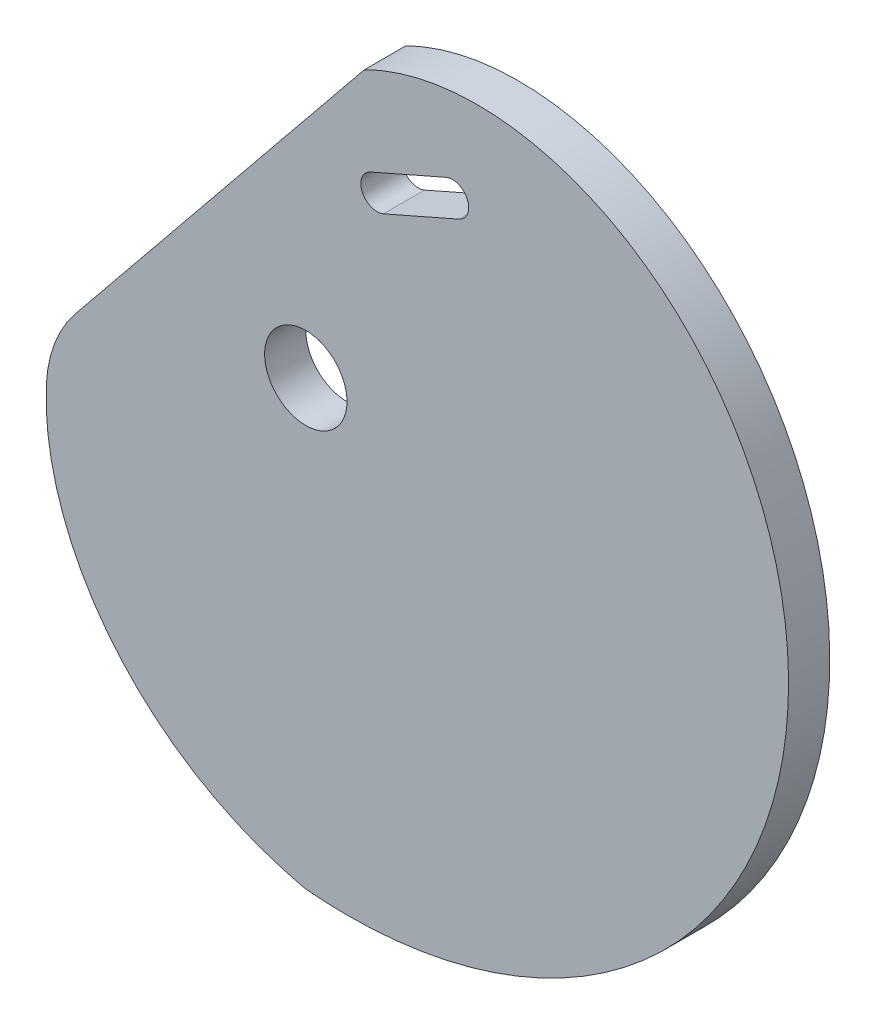
SolidWorks part; units mm, degrees
ref_plane "Front Plane" through (0, 0, 0) normal (0, 0, 1) x (1, 0, 0)
ref_plane "Top Plane" through (0, 0, 0) normal (0, 1, 0) x (1, 0, 0)
ref_plane "Right Plane" through (0, 0, 0) normal (1, 0, 0) x (0, 0, -1)
curve "Curve1"
sketch "Sketch1" plane through (0, 0, 0) normal (0, 0, 1) x (1, 0, 0)
  line L0 (10.9805, 30.1851) -> (22.6104, 35.2876) construction
  line L1 (9.976, 32.4744) -> (21.6059, 37.5769)
  line L2 (11.9849, 27.8957) -> (23.6148, 32.9983)
  line L3 (10.7688, 46.4724) -> (16.7954, 32.7363) construction
  line L4 (-15.5247, -36.542) -> (-17.0714, -47.8252) construction
  line L5 (-12.072, -37.0153) -> (-13.6188, -48.2986) construction
  line L6 (-18.9773, -36.0687) -> (-20.5241, -47.3519) construction
  line L7 (-15.1851, -34.0651) -> (-15.8642, -39.0188) construction
  circle A0 centre (0, 0) radius 6.35
  arc A1 (9.976, 32.4744) -> (11.9849, 27.8957) centre (10.9805, 30.1851) ccw
  arc A2 (23.6148, 32.9983) -> (21.6059, 37.5769) centre (22.6104, 35.2876) ccw
  arc A4 (-12.072, -37.0153) -> (-18.9773, -36.0687) centre (-15.5247, -36.542) ccw construction
  arc A5 (-20.5241, -47.3519) -> (-13.6188, -48.2986) centre (-17.0714, -47.8252) ccw construction
  spline S1 degree 3 poles (-1.1843, -67.9504) (-0.014, -68.2767) (1.195, -68.3213) (2.3889, -68.4148) (3.5889, -68.4701) (4.791, -68.5105) (5.9959, -68.5295) (7.203, -68.5287) (8.412, -68.5074) (9.6226, -68.4657) (10.8344, -68.4032) (12.047, -68.32) (13.2602, -68.2159) (14.4735, -68.0908) (15.6866, -67.9446) (16.8991, -67.777) (18.1106, -67.5882) (19.3207, -67.3779) (20.529, -67.1461) (21.7351, -66.8927) (22.9386, -66.6176) (24.1392, -66.3208) (25.3362, -66.0022) (26.5295, -65.6619) (27.7184, -65.2996) (28.9026, -64.9155) (30.0816, -64.5096) (31.2551, -64.0817) (32.4225, -63.632) (33.5833, -63.1604) (34.7372, -62.667) (35.8837, -62.1518) (37.0223, -61.6149) (38.1525, -61.0563) (39.2739, -60.4761) (40.3861, -59.8743) (41.4885, -59.2512) (42.5806, -58.6068) (43.6621, -57.9411) (44.7324, -57.2544) (45.791, -56.5468) (46.8375, -55.8184) (47.8714, -55.0695) (48.8923, -54.3001) (49.8996, -53.5105) (50.8929, -52.7009) (51.8717, -51.8715) (52.8356, -51.0225) (53.7841, -50.1542) (54.7166, -49.2668) (55.6329, -48.3607) (56.5323, -47.436) (57.4145, -46.4932) (58.279, -45.5324) (59.1254, -44.554) (59.9531, -43.5583) (60.7619, -42.5458) (61.5512, -41.5167) (62.3207, -40.4714) (63.0698, -39.4103) (63.7983, -38.3338) (64.5057, -37.2423) (65.1916, -36.1362) (65.8556, -35.016) (66.4973, -33.882) (67.1165, -32.7348) (67.7126, -31.5748) (68.2854, -30.4026) (68.8345, -29.2185) (69.3596, -28.023) (69.8603, -26.8168) (70.3364, -25.6003) (70.7876, -24.3741) (71.2134, -23.1386) (71.6138, -21.8945) (71.9884, -20.6423) (72.337, -19.3826) (72.6592, -18.116) (72.955, -16.843) (73.224, -15.5643) (73.4661, -14.2804) (73.6812, -12.992) (73.8689, -11.6997) (74.0292, -10.4042) (74.1619, -9.106) (74.2669, -7.8058) (74.3441, -6.5043) (74.3933, -5.2021) (74.4146, -3.9) (74.4078, -2.5984) (74.3729, -1.2982) (74.3098, -0.0001) (74.2186, 1.2954) (74.0993, 2.5875) (73.9518, 3.8756) (73.7762, 5.1589) (73.5725, 6.4367) (73.3409, 7.7084) (73.0814, 8.9732) (72.7942, 10.2305) (72.4792, 11.4795) (72.1368, 12.7196) (71.767, 13.95) (71.3701, 15.1701) (70.9462, 16.3792) (70.4955, 17.5765) (70.0184, 18.7613) (69.515, 19.9331) (68.9856, 21.091) (68.4305, 22.2344) (67.85, 23.3626) (67.2445, 24.475) (66.6143, 25.5709) (65.9598, 26.6495) (65.2813, 27.7103) (64.5793, 28.7526) (63.8542, 29.7758) (63.1064, 30.7792) (62.3364, 31.7621) (61.5447, 32.7241) (60.7318, 33.6643) (59.8981, 34.5824) (59.0442, 35.4776) (58.1707, 36.3494) (57.2782, 37.1972) (56.3671, 38.0204) (55.4383, 38.8186) (54.4923, 39.5913) (53.53, 40.3381) (52.552, 41.0585) (51.5591, 41.7521) (50.552, 42.4186) (49.5315, 43.0576) (48.4984, 43.6687) (47.4535, 44.2516) (46.3974, 44.8061) (45.3311, 45.3318) (44.2553, 45.8284) (43.1709, 46.2958) (42.0786, 46.7338) (40.9793, 47.1421) (39.8737, 47.5205) (38.7628, 47.869) (37.6473, 48.1874) (36.5281, 48.4755) (35.4061, 48.7334) (34.282, 48.961) (33.1567, 49.1581) (32.031, 49.3249) (30.9059, 49.4613) (29.7821, 49.5673) (28.6604, 49.6431) (27.5418, 49.6886) (26.427, 49.7041) (25.3169, 49.6895) (24.2124, 49.6451) (23.1141, 49.571) (22.0231, 49.4674) (20.94, 49.3346) (19.8657, 49.1727) (18.801, 48.982) (17.7468, 48.7628) (16.7037, 48.5154) (15.6726, 48.2401) (14.6543, 47.9373) (13.6495, 47.6073) (12.659, 47.2504) (11.6836, 46.8672) (10.7239, 46.458) (9.7807, 46.0233) (8.8547, 45.5635) (7.9467, 45.0791) (7.0573, 44.5706) (6.1871, 44.0386) (5.3369, 43.4835) (4.5074, 42.906) (3.699, 42.3065) (2.9126, 41.6858) (2.1491, 41.0448) (1.4087, 40.3857) (0.692, 39.711) (-0.0007, 39.0233) (-0.6692, 38.3252) (-1.3135, 37.6192) (-1.9336, 36.908) (-2.5298, 36.194) (-3.1024, 35.4799) (-3.6521, 34.7682) (-4.1795, 34.0612) (-4.6854, 33.3616) (-5.1709, 32.6716) (-5.637, 31.9937) (-6.085, 31.3301) (-6.5163, 30.6831) (-6.9325, 30.0548) (-7.3352, 29.4474) (-7.7263, 28.8629) (-8.1078, 28.3032) (-8.4816, 27.77) (-8.8501, 27.2652) (-9.216, 26.7897) (-9.5801, 26.3424) (-9.9432, 25.9213) (-10.3062, 25.5243) (-10.6698, 25.1494) (-11.0346, 24.7946) (-11.4009, 24.4578) (-11.7691, 24.1369) (-12.1394, 23.8299) (-12.5117, 23.5348) (-12.8861, 23.2497) (-13.2622, 22.9725) (-13.6397, 22.7014) (-14.0182, 22.4345) (-14.3971, 22.1699) (-14.7757, 21.906) (-15.1531, 21.6409) (-15.5285, 21.3732) (-15.9009, 21.1012) (-16.269, 20.8234) (-16.6317, 20.5384) (-16.9875, 20.2449) (-17.3351, 19.9417) (-17.6745, 19.6295) (-18.0059, 19.3089) (-18.3295, 18.9807) (-18.6455, 18.6455) (-18.9542, 18.3039) (-19.2559, 17.9565) (-19.5509, 17.6038) (-19.8396, 17.2464) (-20.1224, 16.8848) (-20.3997, 16.5195) (-20.672, 16.1508) (-20.9397, 15.7793) (-21.2033, 15.4052) (-21.4634, 15.0289) (-21.7205, 14.6507) (-21.9753, 14.2708) (-22.2281, 13.8895) (-22.4798, 13.507) (-22.7308, 13.1233) (-22.9819, 12.7386) (-23.2336, 12.3529) (-23.4866, 11.9663) (-23.7416, 11.5787) (-23.9993, 11.19) (-24.2602, 10.8001) (-24.5251, 10.4088) (-24.7947, 10.016) (-25.0696, 9.6214) (-25.3504, 9.2246) (-25.6379, 8.8254) (-25.9327, 8.4234) (-26.2354, 8.018) (-26.5467, 7.609) (-26.8672, 7.1956) (-27.1974, 6.7776) (-27.537, 6.3539) (-27.8856, 5.9238) (-28.2424, 5.4864) (-28.6069, 5.0408) (-28.9783, 4.5865) (-29.3562, 4.1226) (-29.7396, 3.6485) (-30.1278, 3.1637) (-30.5202, 2.6674) (-30.9158, 2.1592) (-31.314, 1.6386) (-31.7137, 1.1051) (-32.1143, 0.5583) (-32.5148, -0.0021) (-32.9143, -0.5765) (-33.3119, -1.1651) (-33.7067, -1.7682) (-34.0978, -2.3859) (-34.4843, -3.0184) (-34.8652, -3.6658) (-35.2396, -4.3281) (-35.6066, -5.0053) (-35.9651, -5.6973) (-36.3143, -6.404) (-36.6531, -7.1254) (-36.9808, -7.8611) (-37.2963, -8.611) (-37.5988, -9.3748) (-37.8873, -10.1521) (-38.1609, -10.9426) (-38.4187, -11.7459) (-38.66, -12.5613) (-38.8837, -13.3886) (-39.0892, -14.2271) (-39.2755, -15.0762) (-39.4422, -15.9354) (-39.589, -16.8043) (-39.7155, -17.6823) (-39.8215, -18.5689) (-39.9067, -19.4636) (-39.9709, -20.366) (-40.0137, -21.2755) (-40.035, -22.1916) (-40.0345, -23.1138) (-40.0119, -24.0415) (-39.9672, -24.9742) (-39.9002, -25.9114) (-39.8105, -26.8525) (-39.6982, -27.7969) (-39.563, -28.7442) (-39.4048, -29.6936) (-39.2235, -30.6448) (-39.019, -31.597) (-38.7911, -32.5497) (-38.5399, -33.5023) (-38.2653, -34.4543) (-37.9672, -35.4051) (-37.6456, -36.354) (-37.3004, -37.3005) (-36.9317, -38.2441) (-36.5395, -39.184) (-36.1238, -40.1197) (-35.6847, -41.0507) (-35.2221, -41.9763) (-34.7363, -42.896) (-34.2272, -43.8091) (-33.695, -44.715) (-33.1398, -45.6133) (-32.5617, -46.5032) (-31.9609, -47.3843) (-31.3375, -48.2559) (-30.6917, -49.1174) (-30.0238, -49.9683) (-29.3338, -50.808) (-28.6221, -51.636) (-27.8888, -52.4517) (-27.1343, -53.2545) (-26.3587, -54.0439) (-25.5624, -54.8193) (-24.7457, -55.5802) (-23.9088, -56.3261) (-23.0521, -57.0564) (-22.1759, -57.7707) (-21.2805, -58.4684) (-20.3664, -59.149) (-19.4339, -59.812) (-18.4833, -60.4569) (-17.5151, -61.0833) (-16.5298, -61.6908) (-15.5276, -62.2787) (-14.5091, -62.8467) (-13.4747, -63.3944) (-12.4248, -63.9213) (-11.36, -64.4271) (-10.2807, -64.9112) (-9.1874, -65.3733) (-8.0806, -65.8131) (-6.9608, -66.2301) (-5.8286, -66.6239) (-4.6845, -66.9947) (-3.5289, -67.3403) (-2.3631, -67.6669) (-1.1843, -67.9504) (-0.014, -68.2767) (1.195, -68.3213) knots -0.0101 -0.006743 -0.003377 0 0.00332 0.006645 0.009976 0.013312 0.016655 0.020003 0.023357 0.026716 0.030082 0.033453 0.036831 0.040214 0.043603 0.046998 0.050399 0.053806 0.057218 0.060637 0.064061 0.067491 0.070927 0.074369 0.077816 0.081269 0.084728 0.088192 0.091662 0.095138 0.098619 0.102105 0.105597 0.109094 0.112596 0.116103 0.119615 0.123133 0.126655 0.130182 0.133714 0.137251 0.140792 0.144337 0.147888 0.151442 0.155 0.158563 0.16213 0.1657 0.169275 0.172853 0.176434 0.180019 0.183607 0.187199 0.190793 0.19439 0.19799 0.201593 0.205199 0.208806 0.212416 0.216028 0.219642 0.223258 0.226875 0.230494 0.234115 0.237736 0.241359 0.244982 0.248606 0.252231 0.255856 0.259481 0.263106 0.266731 0.270356 0.273981 0.277605 0.281228 0.28485 0.28847 0.29209 0.295708 0.299324 0.302939 0.306551 0.310161 0.313769 0.317374 0.320976 0.324575 0.328171 0.331763 0.335352 0.338938 0.342519 0.346096 0.349669 0.353237 0.356801 0.360359 0.363913 0.367461 0.371004 0.374541 0.378073 0.381598 0.385117 0.38863 0.392136 0.395636 0.399128 0.402614 0.406092 0.409563 0.413026 0.416482 0.419929 0.423369 0.4268 0.430223 0.433637 0.437043 0.44044 0.443828 0.447206 0.450575 0.453935 0.457284 0.460624 0.463953 0.467272 0.47058 0.473877 0.477164 0.480439 0.483703 0.486955 0.490196 0.493426 0.496643 0.499848 0.503042 0.506223 0.509391 0.512547 0.515691 0.518822 0.52194 0.525045 0.528137 0.531216 0.534282 0.537335 0.540375 0.543401 0.546414 0.549414 0.5524 0.555374 0.558333 0.56128 0.564213 0.567133 0.57004 0.572933 0.575814 0.578681 0.581535 0.584377 0.587205 0.590021 0.592825 0.595616 0.598394 0.60116 0.603911 0.606642 0.60935 0.612032 0.614684 0.617303 0.619884 0.622424 0.62492 0.627367 0.629763 0.632104 0.634387 0.636609 0.638767 0.640858 0.64288 0.644831 0.64671 0.648517 0.65025 0.651911 0.653509 0.655048 0.656538 0.657984 0.659394 0.660772 0.662125 0.663458 0.664774 0.666078 0.667373 0.668662 0.669946 0.671227 0.672507 0.673786 0.675065 0.676344 0.677623 0.678903 0.680182 0.681461 0.68274 0.684019 0.685298 0.686575 0.687853 0.689129 0.690404 0.691679 0.692952 0.694224 0.695495 0.696765 0.698035 0.699304 0.700572 0.70184 0.703109 0.704379 0.705651 0.706925 0.708202 0.709483 0.71077 0.712063 0.713364 0.714674 0.715995 0.717328 0.718676 0.72004 0.721422 0.722825 0.72425 0.7257 0.727177 0.728683 0.730218 0.731784 0.73338 0.735008 0.736668 0.738359 0.740082 0.741837 0.743623 0.745441 0.747291 0.749171 0.751082 0.753022 0.754993 0.756992 0.759021 0.761077 0.76316 0.765271 0.767407 0.769569 0.771756 0.773967 0.776201 0.778458 0.780736 0.783036 0.785357 0.787697 0.790056 0.792433 0.794828 0.797239 0.799666 0.80211 0.804571 0.807047 0.80954 0.812049 0.814575 0.817116 0.819674 0.822248 0.824838 0.827444 0.830066 0.832704 0.835358 0.838027 0.840713 0.843414 0.846131 0.848864 0.851612 0.854376 0.857155 0.859949 0.862759 0.865584 0.868424 0.871279 0.874149 0.877033 0.879933 0.882847 0.885776 0.88872 0.891678 0.89465 0.897636 0.900637 0.903651 0.906679 0.909721 0.912777 0.915847 0.91893 0.922026 0.925135 0.928258 0.931393 0.934541 0.937702 0.940876 0.944062 0.947261 0.950471 0.953694 0.956929 0.960175 0.963433 0.966703 0.969984 0.973276 0.976579 0.979893 0.983218 0.986554 0.9899 0.993257 0.996623 1 1.00332 1.006645 1.009976 only from (0, -68.2309) to (0, -68.2309)
  point P6 (16.7954, 32.7363)
  point P18 (-16.298, -42.1836)
  dimension "D1" = 12.7
  dimension "D2" = 12.7
  dimension "D3" = 5
  dimension "D4" = 15
extrude "Boss-Extrude1" add sketch "Sketch1" along normal mid plane 6.35 contours S1 A0 A2 L2 A1 L1 region at (19.1235, -11.794, 0)
sketch "Sketch2" plane through (0, 0, 0) normal (0, 0, 1) x (1, 0, 0)
  line L0 (7.479, 46.6391) -> (-35.7001, -3.6508) construction
  line L1 (-35.7001, -3.6508) -> (-5.287, 46.6391)
  line L2 (-5.287, 46.6391) -> (7.479, 46.6391)
  line L3 (9.0178, 45.6413) -> (-41.2002, -16.1969)
  line L4 (7.479, 46.6391) -> (9.0178, 45.6413)
  line L5 (-35.7001, -3.6508) -> (-41.2002, -16.1969)
  spline S0 degree 3 poles (-1.1843, -67.9504) (-0.014, -68.2767) (1.195, -68.3213) (2.3889, -68.4148) (3.5889, -68.4701) (4.791, -68.5105) (5.9959, -68.5295) (7.203, -68.5287) (8.412, -68.5074) (9.6226, -68.4657) (10.8344, -68.4032) (12.047, -68.32) (13.2602, -68.2159) (14.4735, -68.0908) (15.6866, -67.9446) (16.8991, -67.777) (18.1106, -67.5882) (19.3207, -67.3779) (20.529, -67.1461) (21.7351, -66.8927) (22.9386, -66.6176) (24.1392, -66.3208) (25.3362, -66.0022) (26.5295, -65.6619) (27.7184, -65.2996) (28.9026, -64.9155) (30.0816, -64.5096) (31.2551, -64.0817) (32.4225, -63.632) (33.5833, -63.1604) (34.7372, -62.667) (35.8837, -62.1518) (37.0223, -61.6149) (38.1525, -61.0563) (39.2739, -60.4761) (40.3861, -59.8743) (41.4885, -59.2512) (42.5806, -58.6068) (43.6621, -57.9411) (44.7324, -57.2544) (45.791, -56.5468) (46.8375, -55.8184) (47.8714, -55.0695) (48.8923, -54.3001) (49.8996, -53.5105) (50.8929, -52.7009) (51.8717, -51.8715) (52.8356, -51.0225) (53.7841, -50.1542) (54.7166, -49.2668) (55.6329, -48.3607) (56.5323, -47.436) (57.4145, -46.4932) (58.279, -45.5324) (59.1254, -44.554) (59.9531, -43.5583) (60.7619, -42.5458) (61.5512, -41.5167) (62.3207, -40.4714) (63.0698, -39.4103) (63.7983, -38.3338) (64.5057, -37.2423) (65.1916, -36.1362) (65.8556, -35.016) (66.4973, -33.882) (67.1165, -32.7348) (67.7126, -31.5748) (68.2854, -30.4026) (68.8345, -29.2185) (69.3596, -28.023) (69.8603, -26.8168) (70.3364, -25.6003) (70.7876, -24.3741) (71.2134, -23.1386) (71.6138, -21.8945) (71.9884, -20.6423) (72.337, -19.3826) (72.6592, -18.116) (72.955, -16.843) (73.224, -15.5643) (73.4661, -14.2804) (73.6812, -12.992) (73.8689, -11.6997) (74.0292, -10.4042) (74.1619, -9.106) (74.2669, -7.8058) (74.3441, -6.5043) (74.3933, -5.2021) (74.4146, -3.9) (74.4078, -2.5984) (74.3729, -1.2982) (74.3098, -0.0001) (74.2186, 1.2954) (74.0993, 2.5875) (73.9518, 3.8756) (73.7762, 5.1589) (73.5725, 6.4367) (73.3409, 7.7084) (73.0814, 8.9732) (72.7942, 10.2305) (72.4792, 11.4795) (72.1368, 12.7196) (71.767, 13.95) (71.3701, 15.1701) (70.9462, 16.3792) (70.4955, 17.5765) (70.0184, 18.7613) (69.515, 19.9331) (68.9856, 21.091) (68.4305, 22.2344) (67.85, 23.3626) (67.2445, 24.475) (66.6143, 25.5709) (65.9598, 26.6495) (65.2813, 27.7103) (64.5793, 28.7526) (63.8542, 29.7758) (63.1064, 30.7792) (62.3364, 31.7621) (61.5447, 32.7241) (60.7318, 33.6643) (59.8981, 34.5824) (59.0442, 35.4776) (58.1707, 36.3494) (57.2782, 37.1972) (56.3671, 38.0204) (55.4383, 38.8186) (54.4923, 39.5913) (53.53, 40.3381) (52.552, 41.0585) (51.5591, 41.7521) (50.552, 42.4186) (49.5315, 43.0576) (48.4984, 43.6687) (47.4535, 44.2516) (46.3974, 44.8061) (45.3311, 45.3318) (44.2553, 45.8284) (43.1709, 46.2958) (42.0786, 46.7338) (40.9793, 47.1421) (39.8737, 47.5205) (38.7628, 47.869) (37.6473, 48.1874) (36.5281, 48.4755) (35.4061, 48.7334) (34.282, 48.961) (33.1567, 49.1581) (32.031, 49.3249) (30.9059, 49.4613) (29.7821, 49.5673) (28.6604, 49.6431) (27.5418, 49.6886) (26.427, 49.7041) (25.3169, 49.6895) (24.2124, 49.6451) (23.1141, 49.571) (22.0231, 49.4674) (20.94, 49.3346) (19.8657, 49.1727) (18.801, 48.982) (17.7468, 48.7628) (16.7037, 48.5154) (15.6726, 48.2401) (14.6543, 47.9373) (13.6495, 47.6073) (12.659, 47.2504) (11.6836, 46.8672) (10.7239, 46.458) (9.7807, 46.0233) (8.8547, 45.5635) (7.9467, 45.0791) (7.0573, 44.5706) (6.1871, 44.0386) (5.3369, 43.4835) (4.5074, 42.906) (3.699, 42.3065) (2.9126, 41.6858) (2.1491, 41.0448) (1.4087, 40.3857) (0.692, 39.711) (-0.0007, 39.0233) (-0.6692, 38.3252) (-1.3135, 37.6192) (-1.9336, 36.908) (-2.5298, 36.194) (-3.1024, 35.4799) (-3.6521, 34.7682) (-4.1795, 34.0612) (-4.6854, 33.3616) (-5.1709, 32.6716) (-5.637, 31.9937) (-6.085, 31.3301) (-6.5163, 30.6831) (-6.9325, 30.0548) (-7.3352, 29.4474) (-7.7263, 28.8629) (-8.1078, 28.3032) (-8.4816, 27.77) (-8.8501, 27.2652) (-9.216, 26.7897) (-9.5801, 26.3424) (-9.9432, 25.9213) (-10.3062, 25.5243) (-10.6698, 25.1494) (-11.0346, 24.7946) (-11.4009, 24.4578) (-11.7691, 24.1369) (-12.1394, 23.8299) (-12.5117, 23.5348) (-12.8861, 23.2497) (-13.2622, 22.9725) (-13.6397, 22.7014) (-14.0182, 22.4345) (-14.3971, 22.1699) (-14.7757, 21.906) (-15.1531, 21.6409) (-15.5285, 21.3732) (-15.9009, 21.1012) (-16.269, 20.8234) (-16.6317, 20.5384) (-16.9875, 20.2449) (-17.3351, 19.9417) (-17.6745, 19.6295) (-18.0059, 19.3089) (-18.3295, 18.9807) (-18.6455, 18.6455) (-18.9542, 18.3039) (-19.2559, 17.9565) (-19.5509, 17.6038) (-19.8396, 17.2464) (-20.1224, 16.8848) (-20.3997, 16.5195) (-20.672, 16.1508) (-20.9397, 15.7793) (-21.2033, 15.4052) (-21.4634, 15.0289) (-21.7205, 14.6507) (-21.9753, 14.2708) (-22.2281, 13.8895) (-22.4798, 13.507) (-22.7308, 13.1233) (-22.9819, 12.7386) (-23.2336, 12.3529) (-23.4866, 11.9663) (-23.7416, 11.5787) (-23.9993, 11.19) (-24.2602, 10.8001) (-24.5251, 10.4088) (-24.7947, 10.016) (-25.0696, 9.6214) (-25.3504, 9.2246) (-25.6379, 8.8254) (-25.9327, 8.4234) (-26.2354, 8.018) (-26.5467, 7.609) (-26.8672, 7.1956) (-27.1974, 6.7776) (-27.537, 6.3539) (-27.8856, 5.9238) (-28.2424, 5.4864) (-28.6069, 5.0408) (-28.9783, 4.5865) (-29.3562, 4.1226) (-29.7396, 3.6485) (-30.1278, 3.1637) (-30.5202, 2.6674) (-30.9158, 2.1592) (-31.314, 1.6386) (-31.7137, 1.1051) (-32.1143, 0.5583) (-32.5148, -0.0021) (-32.9143, -0.5765) (-33.3119, -1.1651) (-33.7067, -1.7682) (-34.0978, -2.3859) (-34.4843, -3.0184) (-34.8652, -3.6658) (-35.2396, -4.3281) (-35.6066, -5.0053) (-35.9651, -5.6973) (-36.3143, -6.404) (-36.6531, -7.1254) (-36.9808, -7.8611) (-37.2963, -8.611) (-37.5988, -9.3748) (-37.8873, -10.1521) (-38.1609, -10.9426) (-38.4187, -11.7459) (-38.66, -12.5613) (-38.8837, -13.3886) (-39.0892, -14.2271) (-39.2755, -15.0762) (-39.4422, -15.9354) (-39.589, -16.8043) (-39.7155, -17.6823) (-39.8215, -18.5689) (-39.9067, -19.4636) (-39.9709, -20.366) (-40.0137, -21.2755) (-40.035, -22.1916) (-40.0345, -23.1138) (-40.0119, -24.0415) (-39.9672, -24.9742) (-39.9002, -25.9114) (-39.8105, -26.8525) (-39.6982, -27.7969) (-39.563, -28.7442) (-39.4048, -29.6936) (-39.2235, -30.6448) (-39.019, -31.597) (-38.7911, -32.5497) (-38.5399, -33.5023) (-38.2653, -34.4543) (-37.9672, -35.4051) (-37.6456, -36.354) (-37.3004, -37.3005) (-36.9317, -38.2441) (-36.5395, -39.184) (-36.1238, -40.1197) (-35.6847, -41.0507) (-35.2221, -41.9763) (-34.7363, -42.896) (-34.2272, -43.8091) (-33.695, -44.715) (-33.1398, -45.6133) (-32.5617, -46.5032) (-31.9609, -47.3843) (-31.3375, -48.2559) (-30.6917, -49.1174) (-30.0238, -49.9683) (-29.3338, -50.808) (-28.6221, -51.636) (-27.8888, -52.4517) (-27.1343, -53.2545) (-26.3587, -54.0439) (-25.5624, -54.8193) (-24.7457, -55.5802) (-23.9088, -56.3261) (-23.0521, -57.0564) (-22.1759, -57.7707) (-21.2805, -58.4684) (-20.3664, -59.149) (-19.4339, -59.812) (-18.4833, -60.4569) (-17.5151, -61.0833) (-16.5298, -61.6908) (-15.5276, -62.2787) (-14.5091, -62.8467) (-13.4747, -63.3944) (-12.4248, -63.9213) (-11.36, -64.4271) (-10.2807, -64.9112) (-9.1874, -65.3733) (-8.0806, -65.8131) (-6.9608, -66.2301) (-5.8286, -66.6239) (-4.6845, -66.9947) (-3.5289, -67.3403) (-2.3631, -67.6669) (-1.1843, -67.9504) (-0.014, -68.2767) (1.195, -68.3213) knots -0.0101 -0.006743 -0.003377 0 0.00332 0.006645 0.009976 0.013312 0.016655 0.020003 0.023357 0.026716 0.030082 0.033453 0.036831 0.040214 0.043603 0.046998 0.050399 0.053806 0.057218 0.060637 0.064061 0.067491 0.070927 0.074369 0.077816 0.081269 0.084728 0.088192 0.091662 0.095138 0.098619 0.102105 0.105597 0.109094 0.112596 0.116103 0.119615 0.123133 0.126655 0.130182 0.133714 0.137251 0.140792 0.144337 0.147888 0.151442 0.155 0.158563 0.16213 0.1657 0.169275 0.172853 0.176434 0.180019 0.183607 0.187199 0.190793 0.19439 0.19799 0.201593 0.205199 0.208806 0.212416 0.216028 0.219642 0.223258 0.226875 0.230494 0.234115 0.237736 0.241359 0.244982 0.248606 0.252231 0.255856 0.259481 0.263106 0.266731 0.270356 0.273981 0.277605 0.281228 0.28485 0.28847 0.29209 0.295708 0.299324 0.302939 0.306551 0.310161 0.313769 0.317374 0.320976 0.324575 0.328171 0.331763 0.335352 0.338938 0.342519 0.346096 0.349669 0.353237 0.356801 0.360359 0.363913 0.367461 0.371004 0.374541 0.378073 0.381598 0.385117 0.38863 0.392136 0.395636 0.399128 0.402614 0.406092 0.409563 0.413026 0.416482 0.419929 0.423369 0.4268 0.430223 0.433637 0.437043 0.44044 0.443828 0.447206 0.450575 0.453935 0.457284 0.460624 0.463953 0.467272 0.47058 0.473877 0.477164 0.480439 0.483703 0.486955 0.490196 0.493426 0.496643 0.499848 0.503042 0.506223 0.509391 0.512547 0.515691 0.518822 0.52194 0.525045 0.528137 0.531216 0.534282 0.537335 0.540375 0.543401 0.546414 0.549414 0.5524 0.555374 0.558333 0.56128 0.564213 0.567133 0.57004 0.572933 0.575814 0.578681 0.581535 0.584377 0.587205 0.590021 0.592825 0.595616 0.598394 0.60116 0.603911 0.606642 0.60935 0.612032 0.614684 0.617303 0.619884 0.622424 0.62492 0.627367 0.629763 0.632104 0.634387 0.636609 0.638767 0.640858 0.64288 0.644831 0.64671 0.648517 0.65025 0.651911 0.653509 0.655048 0.656538 0.657984 0.659394 0.660772 0.662125 0.663458 0.664774 0.666078 0.667373 0.668662 0.669946 0.671227 0.672507 0.673786 0.675065 0.676344 0.677623 0.678903 0.680182 0.681461 0.68274 0.684019 0.685298 0.686575 0.687853 0.689129 0.690404 0.691679 0.692952 0.694224 0.695495 0.696765 0.698035 0.699304 0.700572 0.70184 0.703109 0.704379 0.705651 0.706925 0.708202 0.709483 0.71077 0.712063 0.713364 0.714674 0.715995 0.717328 0.718676 0.72004 0.721422 0.722825 0.72425 0.7257 0.727177 0.728683 0.730218 0.731784 0.73338 0.735008 0.736668 0.738359 0.740082 0.741837 0.743623 0.745441 0.747291 0.749171 0.751082 0.753022 0.754993 0.756992 0.759021 0.761077 0.76316 0.765271 0.767407 0.769569 0.771756 0.773967 0.776201 0.778458 0.780736 0.783036 0.785357 0.787697 0.790056 0.792433 0.794828 0.797239 0.799666 0.80211 0.804571 0.807047 0.80954 0.812049 0.814575 0.817116 0.819674 0.822248 0.824838 0.827444 0.830066 0.832704 0.835358 0.838027 0.840713 0.843414 0.846131 0.848864 0.851612 0.854376 0.857155 0.859949 0.862759 0.865584 0.868424 0.871279 0.874149 0.877033 0.879933 0.882847 0.885776 0.88872 0.891678 0.89465 0.897636 0.900637 0.903651 0.906679 0.909721 0.912777 0.915847 0.91893 0.922026 0.925135 0.928258 0.931393 0.934541 0.937702 0.940876 0.944062 0.947261 0.950471 0.953694 0.956929 0.960175 0.963433 0.966703 0.969984 0.973276 0.976579 0.979893 0.983218 0.986554 0.9899 0.993257 0.996623 1 1.00332 1.006645 1.009976 only from (0, -68.2309) to (0, -68.2309) construction
  point P2 (0, 0)
  point P3 (0, 0)
  point P7 (9.0178, 45.6413)
  point P9 (7.6571, 40.7062)
  point P10 (3.8561, 42.4197)
  point P11 (3.8561, 42.4197)
  point P12 (8.8064, 45.5329)
  point P13 (7.479, 46.6391)
extrude "Cut-Extrude1" cut sketch "Sketch2" against normal through all both and the other way through all
fillet "Fillet1" radius 20 1 edges at (-38.8618, -13.3174, 0)
sketch "Sketch3" plane through (0, 0, 3.175) normal (0, 0, 1) x (1, 0, 0)
  point P0 (-13.488, -5.936)
  point P1 (-3.3675, -25.0764)
  point P3 (-25.0038, -24.2708)
sketch "Sketch7" [suppressed] plane through (0, 0, 0) normal (0, 0, 1) x (1, 0, 0)
  circle A0 centre (0, 0) radius 6.35
  circle A1 centre (0, 0) radius 3.175
  dimension "D1" = 6.35
sketch "Sketch8" [suppressed] plane through (0, 0, 0) normal (0, 0, 1) x (1, 0, 0)
  line L0 (10.9805, 30.1851) -> (22.6104, 35.2876) construction
  line L1 (9.976, 32.4744) -> (21.6059, 37.5769)
  line L2 (11.9849, 27.8957) -> (23.6148, 32.9983)
  circle A0 centre (12.6554, 42.1677) radius 1
  arc A1 (5.6152, 38.2953) -> (20.342, 44.5764) centre (12.9786, 41.4359) ccw construction
  circle A2 centre (0, 0) radius 6.35
  arc A3 (9.976, 32.4744) -> (11.9849, 27.8957) centre (10.9805, 30.1851) ccw
  arc A4 (23.6148, 32.9983) -> (21.6059, 37.5769) centre (22.6104, 35.2876) ccw
  arc A5 (23.6148, 32.9983) -> (21.6059, 37.5769) centre (22.6104, 35.2876) ccw construction
  point P12 (16.7954, 32.7363)
  dimension "D2" = 2
  dimension "D1" = 0.8
sketch "Sketch15" plane through (0, 0, 3.175) normal (0, 0, 1) x (1, 0, 0)
  circle A0 centre (-43.3531, -41.4597) radius 1.1
  circle A1 centre (13.5262, -74.2009) radius 1.1
  dimension "D1" = 2.2
  dimension "D2" = 2.2
sketch "Sketch16" plane through (0, 0, 3.175) normal (0, 0, 1) x (1, 0, 0)
  circle A0 centre (-5.523, -52.2474) radius 1.05
  circle A1 centre (5.4449, -44.5935) radius 1.05
  circle A2 centre (10.1611, -19.1035) radius 1.1 construction
  circle A3 centre (-5.523, -52.2474) radius 1.05 construction
  circle A4 centre (5.4449, -44.5935) radius 1.05 construction
  circle A5 centre (10.1611, -19.1035) radius 1.1 construction
sketch "Sketch18" plane through (0, 0, 3.175) normal (0, 0, 1) x (1, 0, 0)
  circle A0 centre (-12.5246, -41.0492) radius 0.7
  circle A1 centre (0, -39.819) radius 0.7
  dimension "D1" = 1.4
  dimension "D2" = 1.4
